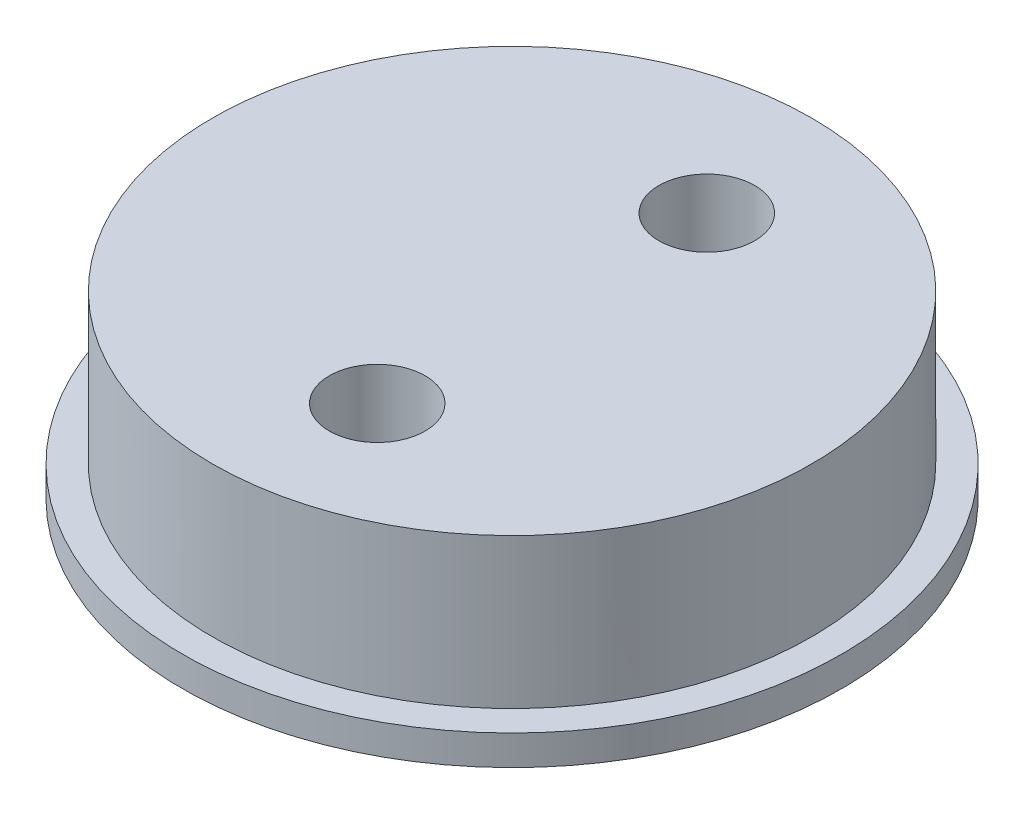
SolidWorks part; units mm, degrees
ref_plane "Front Plane" through (0, 0, 0) normal (0, 0, 1) x (1, 0, 0)
ref_plane "Top Plane" through (0, 0, 0) normal (0, 1, 0) x (1, 0, 0)
ref_plane "Right Plane" through (0, 0, 0) normal (1, 0, 0) x (0, 0, -1)
sketch "Sketch1" plane through (0, 0, 0) normal (0, 1, 0) x (1, 0, 0)
  line L0 (0, 0) -> (-1, 0) construction
  circle A1 centre (-1, 0) radius 10
  point P12 (0, 0)
  dimension "D3" = 20
  dimension "D2" = 1
extrude "Boss-Extrude1" add sketch "Sketch1" along normal blind 6
sketch "Sketch2" plane through (0, 0, 0) normal (0, -1, 0) x (1, 0, 0)
  line L0 (-12.8187, 0) -> (7.6603, 0) construction
  circle A0 centre (-1, 0) radius 11
  dimension "D2" = 22
  dimension "D1" = 1
extrude "Boss-Extrude2" add sketch "Sketch2" against normal blind 1
sketch "Sketch4" plane through (0, 6, 0) normal (0, 1, 0) x (1, 0, 0)
  line L0 (0, 8.8969) -> (0, -8.7328) construction
  circle A0 centre (0, 0) radius 5.5 construction
  circle A4 centre (0, 5.5) radius 1.6
  circle A5 centre (0, -5.5) radius 1.6
  dimension "D1" = 11
  dimension "D2" = 3.2
extrude "Cut-Extrude1" cut sketch "Sketch4" against normal through all
